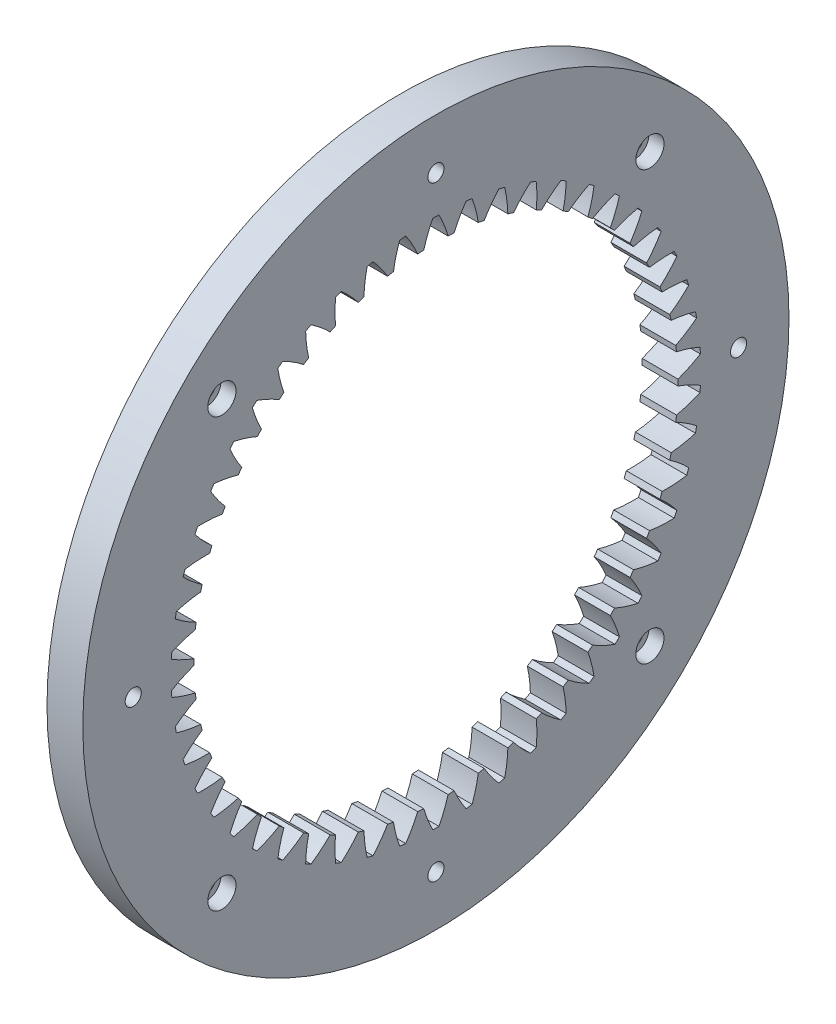
SolidWorks part; units mm, degrees
ref_plane "Plane1" through (0, 0, 0) normal (0, 0, 1) x (1, 0, 0)
ref_plane "Plane2" through (0, 0, 0) normal (0, 1, 0) x (1, 0, 0)
ref_plane "Plane3" through (0, 0, 0) normal (1, 0, 0) x (0, 0, -1)
other "Configuration Table"
sketch "HoldingSke" plane through (0, 0, 0) normal (0, 1, 0) x (1, 0, 0)
  line L0 (0, 0) -> (0.3214, -0.383)
  line L1 (-15, 0) -> (100, 0) construction
  line L2 (0, 0) -> (-2.1039, 2.3779)
  line L3 (0, 0) -> (-11.863, 4.5341)
  line L4 (0, 0) -> (5.5511, 6.6156)
  line L5 (0, 0) -> (-23.7986, -8.8762)
  line L6 (0, 0) -> (-10.5278, -7.1032)
  line L7 (-2.1039, 2.3779) -> (3.3635, 27.1825)
  line L8 (-76.2, 4.3779) -> (-54.61, 4.3779)
  line L9 (-71.009, 38.7566) -> (-53.1078, 45.2721)
  line L10 (-76.2, 71.12) -> (104.1128, 71.12)
  line L11 (0, 0) -> (-15.2, 0)
  line L12 (-76.2, 101.6) -> (-76.133, 101.6)
  line L13 (24.9733, 27.94) -> (52.9518, 28.4284)
  line L14 (24.9733, 27.94) -> (24.9743, 27.94)
  line L15 (24.9733, 27.94) -> (100.4006, 29.5858)
  circle A0 centre (0, 0) radius 70
  circle A1 centre (0, 0) radius 12.7
  circle A2 centre (0, 0) radius 12.7
  dimension "Num_teeth" = 50
  dimension "Pitch_radius" = 180.3128
  dimension "Width" = 15.2
  dimension "Diameter" = 140
sketch "BasProSke" plane through (0, 0, 0) normal (0, 1, 0) x (1, 0, 0)
  line L0 (-10, 0) -> (60, 0) construction
  line L1 (0, 48) -> (0, 70)
  line L2 (0, 48) -> (15.2, 48)
  line L3 (15.2, 48) -> (15.2, 70)
  line L4 (15.2, 70) -> (0, 70)
  dimension "Thickness" = 15.2
  dimension "Diameter" = 140
revolve "Base-Revolve" add sketch "BasProSke" angle 360 about L0
sketch "TooCutSke" plane through (0, 0, 0) normal (1, 0, 0) x (0, 0, -1)
  line L3 (1.738, 49.9698) -> (1.738, 53.6633) construction
  line L4 (0, 0) -> (0, 59.563) construction
  line L5 (0, 0) -> (-4.2903, 68.1927) construction
  line L6 (-21.6015, 41.0107) -> (35.113, 44.5789) construction
  circle A0 centre (0, 0) radius 50 construction
  circle A1 centre (0, 0) radius 52.501 construction
  circle A2 centre (0, 0) radius 42.2862 construction
  circle A3 centre (0, 0) radius 47.9746 construction
  arc A4 (2.4267, 47.9132) -> (0.6033, 52.4975) centre (-21.6015, 41.0107) ccw
  arc A5 (2.4267, 47.9132) -> (-2.4267, 47.9132) centre (0, 0) ccw
  arc A6 (0.6033, 52.4975) -> (-0.6033, 52.4975) centre (0, 0) ccw
  arc A7 (-0.6033, 52.4975) -> (-2.4267, 47.9132) centre (21.6015, 41.0107) ccw
extrude "ToothCut" cut sketch "TooCutSke" along normal through all
fillet "Breaks" [suppressed] radius 0.2
fillet "RootFillets" [suppressed] radius 0.501
pattern_circular "TeethCuts" count 50 every 7.2 about axis through (-10, 0, 0) along (1, 0, 0) of "RootFillets", "Breaks", "ToothCut"
sketch "Sketch1" plane through (15.2, 0, 0) normal (1, 0, 0) x (0, 0, -1)
  circle A0 centre (0, 0) radius 60
  circle A1 centre (0, 60) radius 1.6
  circle A2 centre (60, 0) radius 1.6
  circle A3 centre (0, -60) radius 1.6
  circle A4 centre (-60, 0) radius 1.6
  point P14 (0, 0)
  dimension "D1" = 4
extrude "Cut-Extrude1" cut sketch "Sketch1" against normal blind 16 contours A0 A1 | A0 A1 | A2 | A3 | A4 region at (15.2, 59.3171, 0) region at (15.2, 60.6752, 0)
sketch "Sketch3" plane through (15.2, 0, 0) normal (1, 0, 0) x (0, 0, -1)
  line L0 (0, 0) -> (42.4264, 42.4264) construction
  circle A0 centre (0, 0) radius 60
  circle A1 centre (42.4264, 42.4264) radius 1.6
  circle A2 centre (42.4264, -42.4264) radius 1.6
  circle A3 centre (-42.4264, -42.4264) radius 1.6
  circle A4 centre (-42.4264, 42.4264) radius 1.6
  point P14 (0, 0)
  dimension "D1" = 4
extrude "Cut-Extrude3" cut sketch "Sketch3" against normal blind 16 contours A4 | A1 | A2 | A3
sketch "Sketch8" plane through (15.2, 0, 0) normal (1, 0, 0) x (0, 0, -1)
  circle A1 centre (0, 0) radius 70
  circle A2 centre (0, 0) radius 70
  dimension "D1" = 0
extrude "Cut-Extrude8" cut sketch "Sketch8" against normal blind 8.1
sketch "Sketch10" plane through (7.1, 0, 0) normal (1, 0, 0) x (0, 0, -1)
  circle A0 centre (-42.4264, 42.4264) radius 2.8
  circle A1 centre (42.4264, 42.4264) radius 2.8
  circle A2 centre (42.4264, -42.4264) radius 2.8
  circle A3 centre (-42.4264, -42.4264) radius 2.8
  point P12 (0, 0)
  dimension "D1" = 4
extrude "Cut-Extrude10" cut sketch "Sketch10" against normal blind 3
sketch "Sketch11" plane through (0, 0, 0) normal (-1, 0, 0) x (0, 0, 1)
  line L0 (63.2332, 0) -> (61.6166, 2.8)
  line L1 (0, 63.2332) -> (-2.8, 61.6166)
  line L2 (-2.8, 61.6166) -> (-2.8, 58.3834)
  line L3 (-2.8, 58.3834) -> (0, 56.7668)
  line L4 (0, 56.7668) -> (2.8, 58.3834)
  line L5 (2.8, 58.3834) -> (2.8, 61.6166)
  line L6 (2.8, 61.6166) -> (0, 63.2332)
  line L7 (61.6166, 2.8) -> (58.3834, 2.8)
  line L8 (58.3834, 2.8) -> (56.7668, 0)
  line L9 (56.7668, 0) -> (58.3834, -2.8)
  line L10 (58.3834, -2.8) -> (61.6166, -2.8)
  line L11 (61.6166, -2.8) -> (63.2332, 0)
  line L12 (0, -63.2332) -> (2.8, -61.6166)
  line L13 (2.8, -61.6166) -> (2.8, -58.3834)
  line L14 (2.8, -58.3834) -> (0, -56.7668)
  line L15 (0, -56.7668) -> (-2.8, -58.3834)
  line L16 (-2.8, -58.3834) -> (-2.8, -61.6166)
  line L17 (-2.8, -61.6166) -> (0, -63.2332)
  line L18 (-63.2332, 0) -> (-61.6166, -2.8)
  line L19 (-61.6166, -2.8) -> (-58.3834, -2.8)
  line L20 (-58.3834, -2.8) -> (-56.7668, 0)
  line L21 (-56.7668, 0) -> (-58.3834, 2.8)
  line L22 (-58.3834, 2.8) -> (-61.6166, 2.8)
  line L23 (-61.6166, 2.8) -> (-63.2332, 0)
  circle A0 centre (0, 60) radius 2.8 construction
  point P30 (0, 0)
  dimension "D1" = 4
extrude "Cut-Extrude11" cut sketch "Sketch11" against normal blind 3
equation "' \"Module@HoldingSke\" = 6.35"
equation "' \"Num_teeth@HoldingSke\" = 24"
equation "' \"Ap@HoldingSke\" =  14.5"
equation "' \"Ap@HoldingSke\" = 14.5"
equation "' \"Width@HoldingSke\" = 12"
equation "' \"Diameter@HoldingSke\" = 8 * 25.4"
equation "' \"Show_teeth@HoldingSke\" = 100"
equation "' \"Backlash@HoldingSke\" = 0.009 * 25.4"
equation "' \"Addendum_fac@HoldingSke\" = 1.0"
equation "' \"Dedendum_fac@HoldingSke\" = 1.25"
equation "' \"Dedendum_add@HoldingSke\" = 0.00005 * 25.4"
equation "' \"Clearance_fac@HoldingSke\" = 0.25"
equation "\"Pitch@HoldingSke\" = 1 / \"Module@HoldingSke\" "
equation "\"Overcut_dia@TooCutSke\" = (\"Num_teeth@HoldingSke\" - 2 * \"Addendum_fac@HoldingSke\") / \"Pitch@HoldingSke\" - 0.002 * 25.4"
equation "\"Pitch_dia@TooCutSke\" = \"Num_teeth@HoldingSke\" / \"Pitch@HoldingSke\""
equation "\"Base_dia@TooCutSke\" = \"Num_teeth@HoldingSke\" / \"Pitch@HoldingSke\" * cos((\"Ap@HoldingSke\"  * 3.14159265 / 180)) * 0.90"
equation "\"Root_dia@TooCutSke\" = \"Num_teeth@HoldingSke\"  / \"Pitch@HoldingSke\" + 2 *  \"Dedendum_fac@HoldingSke\"/ \"Pitch@HoldingSke\" + \"Dedendum_add@HoldingSke\" * 2"
equation "\"Half_ang@TooCutSke\" = 180 / \"Num_teeth@HoldingSke\""
equation "\"Half_CT@TooCutSke\" = \"Num_teeth@HoldingSke\" / \"Pitch@HoldingSke\" * sin((3.14159265 / 2 / \"Num_teeth@HoldingSke\")) / 2 + 10 * \"Backlash@HoldingSke\" / 4"
equation "\"Flank_rad@TooCutSke\" = \"Num_teeth@HoldingSke\" / \"Pitch@HoldingSke\" / 4"
equation "\"Radius@RootFillets\"= \"Clearance_fac@HoldingSke\" / \"Pitch@HoldingSke\" + \"Dedendum_add@HoldingSke\""
equation "\"Break_rad@Breaks\" = 0.02 / \"Pitch@HoldingSke\" * 5"
equation "\"Num_teeth@TeethCuts\" = int( \"Show_teeth@HoldingSke\" ) + 1"
equation "\"Num_teeth@TeethCuts\" = ((sgn( \"Num_teeth@TeethCuts\" - \"Num_teeth@HoldingSke\" )-1)*( \"Num_teeth@TeethCuts\" - \"Num_teeth@HoldingSke\" ))/-2+ \"Num_teeth@HoldingSke\""
equation "\"Num_teeth@TeethCuts\" = ((sgn( \"Num_teeth@TeethCuts\" - 2.0)+1)*( \"Num_teeth@TeethCuts\" - 2.0))/2 +2.0"
equation "\"Angle@TeethCuts\" = 360.0 / \"Num_teeth@HoldingSke\""
equation "\"Diameter@BasProSke\" = \"Num_teeth@HoldingSke\"  / \"Pitch@HoldingSke\" + 2 *  \"Dedendum_fac@HoldingSke\"/ \"Pitch@HoldingSke\" + \"Dedendum_add@HoldingSke\" * 2 + 0.002 * 25.4"
equation "\"Diameter@BasProSke\" = ((sgn( \"Diameter@BasProSke\"  - \"Diameter@HoldingSke\" )+1)*( \"Diameter@BasProSke\"  - \"Diameter@HoldingSke\" ))/2 + \"Diameter@HoldingSke\""
equation "\"Inside_diameter@BasProSke\" =  (\"Num_teeth@HoldingSke\" - 2 * \"Addendum_fac@HoldingSke\") / \"Pitch@HoldingSke\" "
equation "\"Thickness@BasProSke\"  = \"Width@HoldingSke\""
